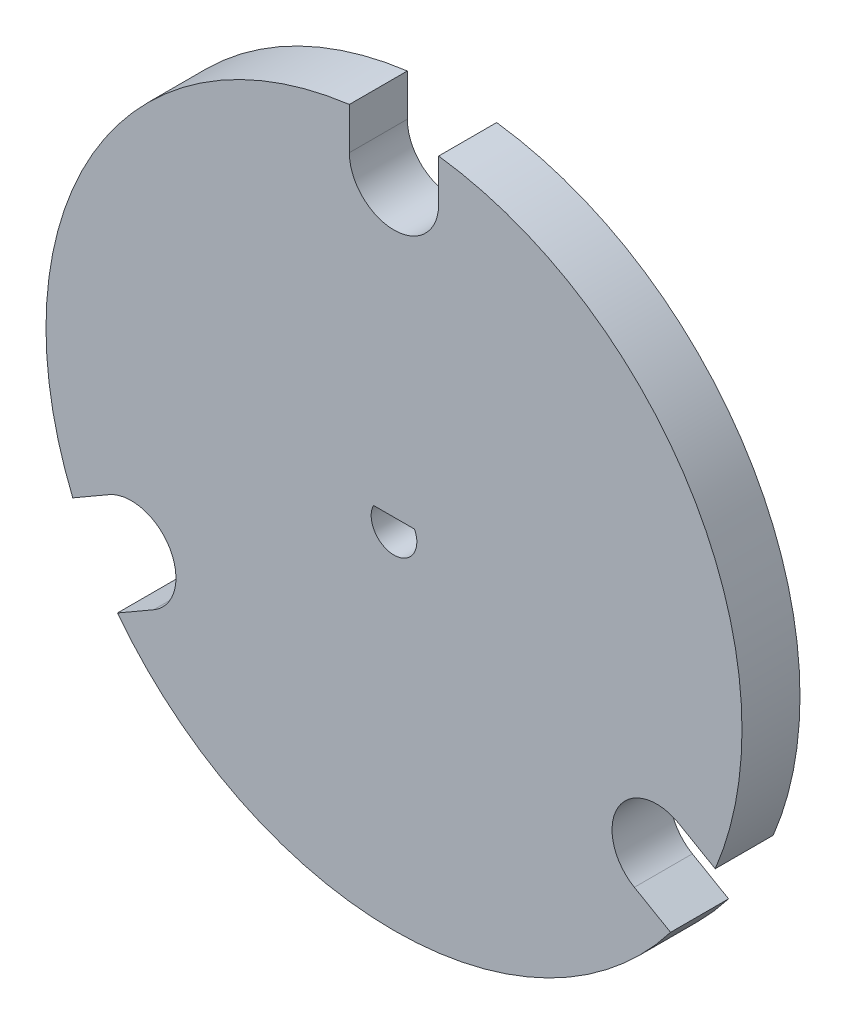
SolidWorks part; units mm, degrees
material "Acrylic (Medium-high impact)"
ref_plane "Front Plane" through (0, 0, 0) normal (0, 0, 1) x (1, 0, 0)
ref_plane "Top Plane" through (0, 0, 0) normal (0, 1, 0) x (1, 0, 0)
ref_plane "Right Plane" through (0, 0, 0) normal (1, 0, 0) x (0, 0, -1)
sketch "Sketch1" plane through (0, 0, 0) normal (0, 0, 1) x (1, 0, 0)
  circle A0 centre (0, 0) radius 38.1
  dimension "D1" = 76.2
extrude "Boss-Extrude1" add sketch "Sketch1" along normal blind 6.35
sketch "Sketch2" plane through (0, 0, 6.35) normal (0, 0, 1) x (1, 0, 0)
  line L0 (-4.8895, 33.2105) -> (-4.8895, 37.785)
  line L1 (0, 33.2105) -> (-28.7611, -16.6052) construction
  line L2 (-28.7611, -16.6052) -> (28.7611, -16.6052) construction
  line L3 (28.7611, -16.6052) -> (0, 33.2105) construction
  line L4 (4.8895, 33.2105) -> (4.8895, 37.785)
  line L5 (31.2059, -12.3708) -> (35.1675, -14.658)
  line L6 (26.3164, -20.8397) -> (30.278, -23.1269)
  line L7 (-26.3164, -20.8397) -> (-30.278, -23.1269)
  line L8 (-31.2059, -12.3708) -> (-35.1675, -14.658)
  circle A0 centre (0, 0) radius 16.6052 construction
  arc A1 (-4.8895, 33.2105) -> (4.8895, 33.2105) centre (0, 33.2105) ccw
  circle A2 centre (0, 0) radius 38.1 construction
  arc A3 (-4.8895, 37.785) -> (4.8895, 37.785) centre (0, 0) cw
  arc A4 (31.2059, -12.3708) -> (26.3164, -20.8397) centre (28.7611, -16.6052) ccw
  arc A5 (35.1675, -14.658) -> (30.278, -23.1269) centre (0, 0) cw
  arc A6 (-26.3164, -20.8397) -> (-31.2059, -12.3708) centre (-28.7611, -16.6053) ccw
  arc A7 (-30.278, -23.1269) -> (-35.1675, -14.658) centre (0, 0) cw
  point P25 (0, 0)
  dimension "D1" = 9.779
  dimension "D2" = 3
extrude "Cut-Extrude1" cut sketch "Sketch2" against normal through all
sketch "Sketch3" plane through (0, 0, 6.35) normal (0, 0, 1) x (1, 0, 0)
  line L0 (-2.25, 1.0897) -> (2.25, 1.0897)
  arc A0 (-2.25, 1.0897) -> (2.25, 1.0897) centre (0, 0) ccw
  dimension "D1" = 5
  dimension "D2" = 4.5
extrude "Cut-Extrude2" cut sketch "Sketch3" against normal through all
